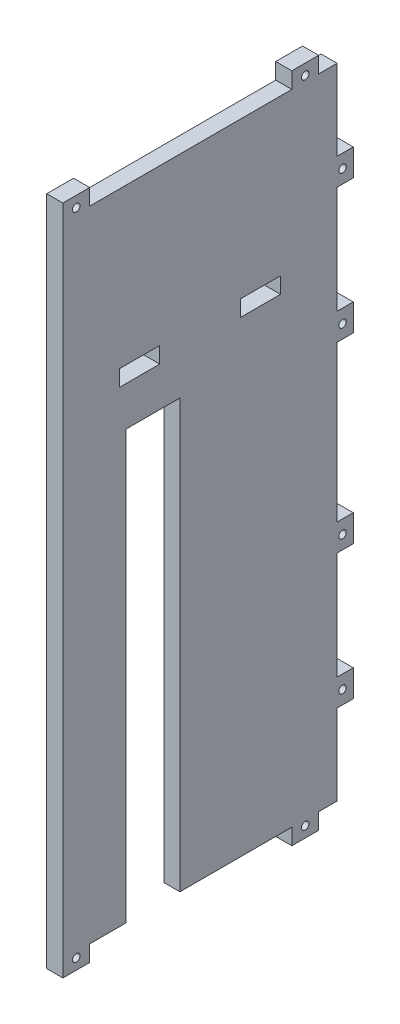
SolidWorks part; units mm, degrees
ref_plane "Plan de face" through (0, 0, 0) normal (0, 0, 1) x (1, 0, 0)
ref_plane "Plan de dessus" through (0, 0, 0) normal (0, 1, 0) x (1, 0, 0)
ref_plane "Plan de droite" through (0, 0, 0) normal (1, 0, 0) x (0, 0, -1)
sketch "Esquisse1" plane through (0, 0, 0) normal (1, 0, 0) x (0, 0, -1)
  line L0 (97.1531, 0) -> (-102.2664, 0) construction
  line L1 (-51.085, 119) -> (51.085, 119)
  line L2 (-51.085, 119) -> (-51.085, -119)
  line L3 (-51.085, -119) -> (51.085, -119)
  line L4 (51.085, 119) -> (51.085, -119)
  line L5 (0, 172.7153) -> (0, -236.1933) construction
  line L15 (-30, 61) -> (-15, 61)
  line L16 (-30, 61) -> (-30, 55)
  line L17 (-30, 55) -> (-15, 55)
  line L18 (-15, 61) -> (-15, 55)
  line L19 (15, 61) -> (30, 61)
  line L20 (15, 61) -> (15, 55)
  line L21 (15, 55) -> (30, 55)
  line L22 (30, 61) -> (30, 55)
  dimension "D1" = 238
  dimension "D2" = 102.17
  dimension "D4" = 119
  dimension "D13" = 15
  dimension "D14" = 15
  dimension "D15" = 30
  dimension "D16" = 6
  dimension "D17" = 6
  dimension "D3" = 51.085
  dimension "D5" = 58
  dimension "D6" = 21.085
extrude "Boss.-Extru.1" add sketch "Esquisse1" along normal blind 6
sketch "Esquisse3" plane through (6, 0, 0) normal (1, 0, 0) x (0, 0, -1)
  line L0 (-51.085, -119) -> (51.085, -119) construction
  line L1 (-51.085, -119) -> (-41.085, -119)
  line L2 (-51.085, -119) -> (-51.085, -125)
  line L3 (-51.085, -125) -> (-41.085, -125)
  line L4 (-41.085, -119) -> (-41.085, -125)
  line L5 (245.3741, 0) -> (-166.5298, 0) construction
  line L6 (51.085, -119) -> (51.085, 119) construction
  line L7 (34.205, -119) -> (44.205, -119)
  line L8 (34.205, -119) -> (34.205, -125)
  line L9 (34.205, -125) -> (44.205, -125)
  line L10 (0, 208.6671) -> (0, -232.3841) construction
  line L12 (44.205, -119) -> (44.205, -125)
  line L13 (51.085, 89) -> (57.085, 89)
  line L14 (51.085, 89) -> (51.085, 79)
  line L15 (51.085, 79) -> (57.085, 79)
  line L16 (57.085, 89) -> (57.085, 79)
  line L17 (51.085, 39) -> (57.085, 39)
  line L18 (51.085, 39) -> (51.085, 29)
  line L19 (51.085, 29) -> (57.085, 29)
  line L20 (57.085, 39) -> (57.085, 29)
  line L21 (57.085, -39) -> (57.085, -29)
  line L22 (51.085, -29) -> (57.085, -29)
  line L23 (51.085, -39) -> (51.085, -29)
  line L24 (51.085, -39) -> (57.085, -39)
  line L25 (57.085, -89) -> (57.085, -79)
  line L26 (51.085, -79) -> (57.085, -79)
  line L27 (51.085, -89) -> (51.085, -79)
  line L28 (51.085, -89) -> (57.085, -89)
  line L29 (0, -208.6671) -> (0, 232.3841) construction
  line L46 (44.205, 119) -> (44.205, 125)
  line L47 (34.205, 125) -> (44.205, 125)
  line L48 (34.205, 119) -> (34.205, 125)
  line L49 (34.205, 119) -> (44.205, 119)
  line L50 (-41.085, 119) -> (-41.085, 125)
  line L51 (-51.085, 125) -> (-41.085, 125)
  line L52 (-51.085, 119) -> (-51.085, 125)
  line L53 (-51.085, 119) -> (-41.085, 119)
  dimension "D2" = 10
  dimension "D3" = 6
  dimension "D4" = 10
  dimension "D5" = 6.88
  dimension "D6" = 6
  dimension "D7" = 10
  dimension "D8" = 6
  dimension "D9" = 6
  dimension "D10" = 10
extrude "Boss.-Extru.5" add sketch "Esquisse3" against normal blind 6
sketch "Esquisse4" plane through (6, 0, 0) normal (1, 0, 0) x (0, 0, -1)
  line L0 (57.085, -29) -> (51.085, -29) construction
  line L1 (57.085, -39) -> (57.085, -29) construction
  line L2 (57.085, -89) -> (57.085, -79) construction
  line L3 (57.085, -79) -> (51.085, -79) construction
  line L10 (-51.085, -125) -> (-41.085, -125) construction
  line L11 (-51.085, 125) -> (-51.085, -125) construction
  line L14 (0, 149.5198) -> (0, -197.2248) construction
  line L15 (203.7475, 0) -> (-122.4342, 0) construction
  line L16 (0, -149.5198) -> (0, 197.2248) construction
  line L17 (34.205, -119) -> (34.205, -125) construction
  line L18 (34.205, -125) -> (44.205, -125) construction
  circle A0 centre (39.205, -121) radius 1.4
  circle A1 centre (53.085, -84) radius 1.4
  circle A2 centre (53.085, -34) radius 1.4
  circle A3 centre (-46.085, 121) radius 1.4
  circle A4 centre (53.085, 34) radius 1.4
  circle A5 centre (53.085, 84) radius 1.4
  circle A8 centre (39.205, 121) radius 1.4
  circle A15 centre (-46.085, -121) radius 1.4
  point P0 (54.085, -29)
  point P35 (34.205, -122)
  dimension "D2" = 2.8
  dimension "D3" = 2.8
  dimension "D4" = 4
  dimension "D5" = 2.8
  dimension "D6" = 5
  dimension "D7" = 5
  dimension "D8" = 4
  dimension "D9" = 4
  dimension "D10" = 2.8
  dimension "D11" = 5
  dimension "D12" = 4
  dimension "D13" = 5
extrude "Enlèv. mat.-Extru.1" cut sketch "Esquisse4" against normal blind 6
sketch "Esquisse6" plane through (6, 0, 0) normal (1, 0, 0) x (0, 0, -1)
  line L0 (-41.085, -119) -> (34.205, -119) construction
  line L1 (-27.485, -119) -> (-7.485, -119)
  line L2 (-27.485, -119) -> (-27.485, 40.29)
  line L3 (-27.485, 40.29) -> (-7.485, 40.29)
  line L4 (-7.485, -119) -> (-7.485, 40.29)
  line L5 (51.085, -29) -> (51.085, 29) construction
  line L6 (-41.085, 125) -> (-51.085, 125) construction
  dimension "D1" = 20
  dimension "D2" = 84.71
  dimension "D3" = 58.57
extrude "Enlèv. mat.-Extru.2" cut sketch "Esquisse6" against normal blind 6
equation "\"D3@Esquisse1\"=\"D2@Esquisse1\"/2"
equation "\"D4@Esquisse1\"=\"D1@Esquisse1\"/2"
